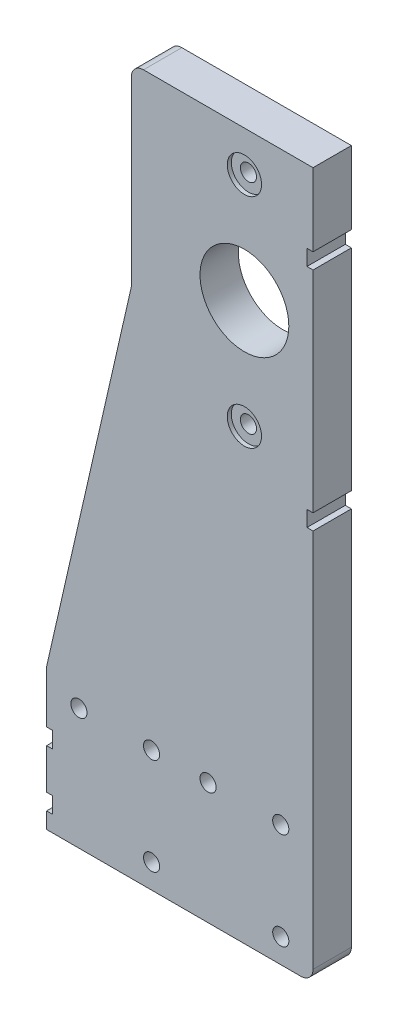
SolidWorks part; units mm, degrees
ref_plane "前视基准面" through (0, 0, 0) normal (0, 0, 1) x (1, 0, 0)
ref_plane "上视基准面" through (0, 0, 0) normal (0, 1, 0) x (1, 0, 0)
ref_plane "右视基准面" through (0, 0, 0) normal (1, 0, 0) x (0, 0, -1)
sketch "草图10" plane through (0, 0, 0) normal (0, 0, 1) x (1, 0, 0)
  line L0 (0, 0) -> (66, 0)
  line L1 (66, 0) -> (66, 175)
  line L2 (66, 175) -> (21, 175)
  line L3 (21, 175) -> (21, 127)
  line L4 (21, 127) -> (0, 35)
  line L5 (0, 35) -> (0, 0)
  line L6 (49, 175) -> (49, 0) construction
  dimension "D1" = 66
  dimension "D2" = 175
  dimension "D3" = 45
  dimension "D4" = 48
  dimension "D5" = 35
  dimension "D6" = 17
extrude "凸台-拉伸4" add sketch "草图10" along normal blind 9.5 contours L4 L5 L0 L1 L2 L3
sketch "草图11" plane through (0, 0, 9.5) normal (0, 0, 1) x (1, 0, 0)
  line L0 (49, 175) -> (49, 0) construction
  line L1 (66, 175) -> (21, 175) construction
  line L2 (0, 0) -> (66, 0) construction
  line L3 (66, 0) -> (66, 175) construction
  circle A0 centre (49, 165) radius 2
  circle A1 centre (49, 111) radius 2
  dimension "D1" = 4
  dimension "D2" = 10
  dimension "D3" = 54
  dimension "D4" = 17
extrude "切除-拉伸8" cut sketch "草图11" against normal through all contours A1 | A0
sketch "草图12" plane through (0, 0, 9.5) normal (0, 0, 1) x (1, 0, 0)
  circle A0 centre (49, 165) radius 4.25
  circle A1 centre (49, 111) radius 4.25
  circle A2 centre (49, 165) radius 2 construction
  dimension "D1" = 8.5
extrude "切除-拉伸9" cut sketch "草图12" against normal blind 1
fillet "圆角7" radius 3 3 edges at (66, 0, 4.75) (21, 127, 4.75) (21, 175, 4.75)
sketch "草图13" plane through (0, 0, 9.5) normal (0, 0, 1) x (1, 0, 0)
  line L0 (49, 165) -> (49, 51.4877) construction
sketch "草图19" plane through (0, 0, 9.5) normal (0, 0, 1) x (1, 0, 0)
  circle A1 centre (49, 138) radius 11
  dimension "D1" = 22
extrude "切除-拉伸11" cut sketch "草图19" against normal through all
sketch "草图21" plane through (0, 0, 0) normal (-1, 0, 0) x (0, 0, 1)
  line L0 (0, 35) -> (0, 0) construction
  line L5 (9.5, 35) -> (9.5, 0) construction
  line L7 (0, 8) -> (9.5, 8)
  line L8 (0, 8) -> (0, 4)
  line L9 (0, 4) -> (9.5, 4)
  line L10 (9.5, 8) -> (9.5, 4)
  line L11 (0, 22) -> (9.5, 22)
  line L12 (0, 22) -> (0, 18)
  line L13 (0, 18) -> (9.5, 18)
  line L14 (9.5, 22) -> (9.5, 18)
extrude "切除-拉伸12" cut sketch "草图21" against normal blind 1.5
sketch "草图22" plane through (66, 0, 0) normal (1, 0, 0) x (0, 0, -1)
  line L0 (0, 3) -> (0, 175) construction
  line L5 (-9.5, 3) -> (-9.5, 175) construction
  line L7 (-9.5, 100.95) -> (0, 100.95)
  line L8 (-9.5, 100.95) -> (-9.5, 97.05)
  line L9 (-9.5, 97.05) -> (0, 97.05)
  line L10 (0, 100.95) -> (0, 97.05)
  line L11 (-9.5, 156.95) -> (0, 156.95)
  line L12 (-9.5, 156.95) -> (-9.5, 153.05)
  line L13 (-9.5, 153.05) -> (0, 153.05)
  line L14 (0, 156.95) -> (0, 153.05)
extrude "切除-拉伸13" cut sketch "草图22" against normal blind 1.5
sketch "草图26" plane through (0, 0, 0) normal (0, 0, -1) x (-1, 0, 0)
  circle A0 centre (-49, 165) radius 4
  circle A1 centre (-49, 111) radius 4
  dimension "D1" = 8
extrude "切除-拉伸18" cut sketch "草图26" against normal blind 4
sketch "草图27" plane through (0, 0, 9.5) normal (0, 0, 1) x (1, 0, 0)
  circle A0 centre (8, 30.03) radius 2
  circle A1 centre (26, 30.03) radius 2
  circle A2 centre (40, 30.03) radius 2
  circle A3 centre (58, 30.03) radius 2
  circle A4 centre (58, 6.03) radius 2
  circle A5 centre (26, 6.03) radius 2
  dimension "D1" = 4
extrude "切除-拉伸19" cut sketch "草图27" against normal through all
sketch "草图28" plane through (0, 0, 0) normal (0, 0, -1) x (-1, 0, 0)
  circle A0 centre (-58, 30.03) radius 4
  circle A1 centre (-40, 30.03) radius 4
  circle A2 centre (-26, 30.03) radius 4
  circle A3 centre (-8, 30.03) radius 4
  circle A4 centre (-58, 6.03) radius 4
  circle A5 centre (-26, 6.03) radius 4
  dimension "D1" = 8
extrude "切除-拉伸20" cut sketch "草图28" against normal blind 4
